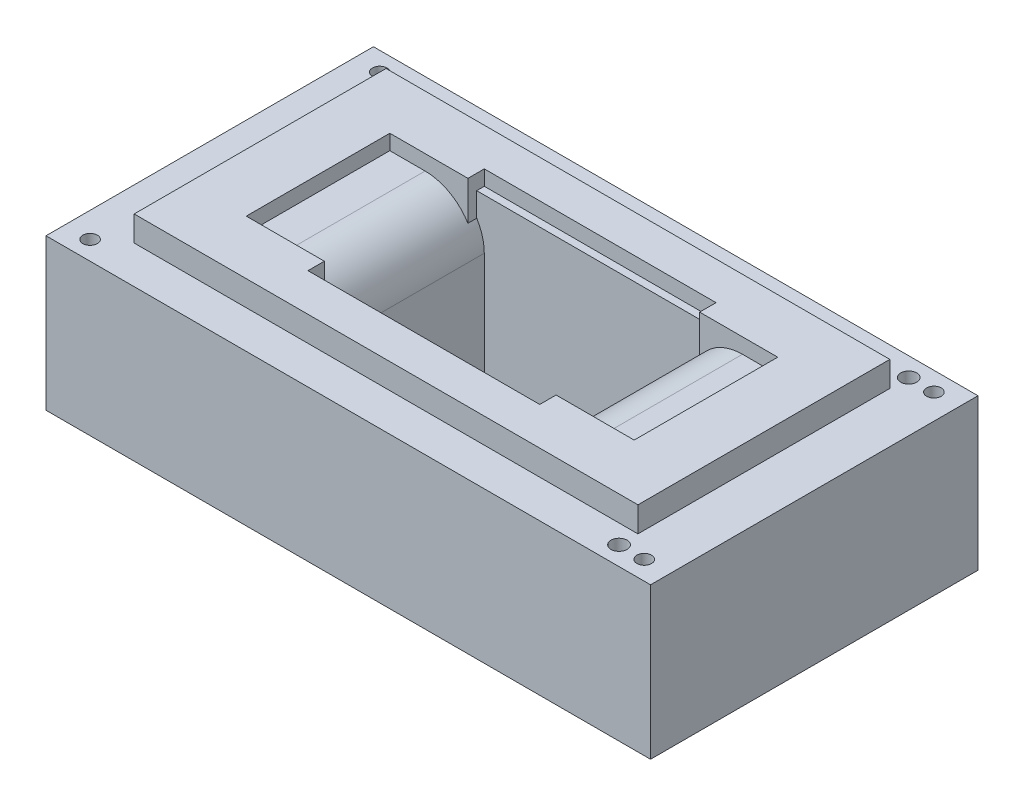
SolidWorks part; units mm, degrees
ref_plane "Front Plane" through (0, 0, 0) normal (0, 0, 1) x (1, 0, 0)
ref_plane "Top Plane" through (0, 0, 0) normal (0, 1, 0) x (1, 0, 0)
ref_plane "Right Plane" through (0, 0, 0) normal (1, 0, 0) x (0, 0, -1)
sketch "Sketch1" plane through (0, 0, 0) normal (0, 1, 0) x (1, 0, 0)
  line L0 (23, -14.25) -> (23, -17.5)
  line L7 (-50, 25) -> (50, 25)
  line L8 (-50, 25) -> (-50, -25)
  line L9 (-50, -25) -> (50, -25)
  line L10 (50, 25) -> (50, -25)
  line L11 (-50, 25) -> (50, -25) construction
  line L12 (-50, -25) -> (23, 11.5) construction
  line L15 (-38.5, 14.25) -> (-23, 14.25)
  line L16 (-38.5, 14.25) -> (-38.5, -14.25)
  line L17 (-38.5, -14.25) -> (-23, -14.25)
  line L18 (38.5, 14.25) -> (38.5, -14.25)
  line L19 (-38.5, 14.25) -> (38.5, -14.25) construction
  line L20 (-38.5, -14.25) -> (38.5, 14.25) construction
  line L21 (-23, 17.5) -> (23, 17.5)
  line L22 (-23, 17.5) -> (-23, 14.25)
  line L23 (-23, -17.5) -> (23, -17.5)
  line L24 (23, 17.5) -> (23, 14.25)
  line L25 (-23, 17.5) -> (23, -17.5) construction
  line L26 (-23, -17.5) -> (23, 17.5) construction
  line L27 (-23, -14.25) -> (-23, -17.5)
  line L28 (28.5, 14.25) -> (50, 25) construction
  line L29 (23, -14.25) -> (38.5, -14.25)
  line L30 (23, 14.25) -> (38.5, 14.25)
  point P0 (0, 0)
  point P1 (0, 0)
  point P2 (0, 0)
  point P6 (0, 0)
  point P17 (0, 0)
  point P18 (0, 0)
  dimension "D1" = 28.5
  dimension "D2" = 77
  dimension "D3" = 50
  dimension "D4" = 100
  dimension "D5" = 46
  dimension "D6" = 35
extrude "Boss-Extrude3" add sketch "Sketch1" along normal blind 2 contours L16 L17 L27 L23 L0 L29 L18 L30 L24 L21 L22 L15
extrude "Boss-Extrude4" add sketch "Sketch1<6>" along normal blind 5
sketch "Sketch1<6>" plane through (0, 0, 0) normal (0, 1, 0) x (1, 0, 0) same geometry as "Sketch1"
sketch "Sketch2" plane through (0, 0, 0) normal (0, -1, 0) x (1, 0, 0)
  line L0 (-60, 32.5) -> (-50, 25) construction
  line L1 (-60, 32.5) -> (60, 32.5)
  line L2 (-60, 32.5) -> (-60, -32.5)
  line L3 (-60, -32.5) -> (60, -32.5)
  line L4 (60, 32.5) -> (60, -32.5)
  line L5 (-60, 32.5) -> (60, -32.5) construction
  line L6 (-60, -32.5) -> (60, 32.5) construction
  line L7 (-55.7374, 27.7668) -> (-54.2626, 29.7332) construction
  line L8 (0, 0) -> (0, -0.0408) construction
  line L9 (-0.0011, 0) -> (0.0027, 0) construction
  circle A0 centre (-55, 28.75) radius 1.45
  circle A1 centre (55, 28.75) radius 1.45
  circle A2 centre (55, -28.75) radius 1.45
  circle A3 centre (-55, -28.75) radius 1.45
  circle A4 centre (50, 28.75) radius 1.6
  circle A5 centre (50, -28.75) radius 1.6
  point P0 (0, 0)
  point P14 (-55, 28.75)
  point P27 (0, 0)
  dimension "D3" = 2.9
  dimension "D4" = 105
  dimension "D5" = 3.2
  dimension "D1" = 65
  dimension "D2" = 120
extrude "Boss-Extrude5" add sketch "Sketch2" along normal blind 30
sketch "Sketch3" plane through (0, -30, 0) normal (0, -1, 0) x (-1, 0, 0)
extrude "Boss-Extrude6" add sketch "Sketch2<2>" along normal blind 3
sketch "Sketch2<2>" plane through (0, 0, 0) normal (0, -1, 0) x (1, 0, 0) same geometry as "Sketch2"
sketch "Sketch6" plane through (0, 5, 0) normal (0, 1, 0) x (1, 0, 0)
  line L0 (-60, 32.5) -> (60, 32.5) construction
  line L5 (-38.5, 14.25) -> (-38.5, 20.6736) construction
  line L6 (60, -32.5) -> (-60, -32.5) construction
  line L7 (0.9, -32.5) -> (20.9, -32.5)
  line L8 (0.9, -32.5) -> (0.9, -7.9646)
  line L9 (0.9, -7.9646) -> (20.9, -7.9646)
  line L10 (20.9, -32.5) -> (20.9, -7.9646)
  line L11 (-38.5, -14.25) -> (-23, -14.25) construction
  line L12 (-38.5, 20.6736) -> (38.5, 20.6736) construction
  line L13 (38.5, 14.25) -> (38.5, 20.6736) construction
  line L14 (0, 20.6736) -> (0, -12.65) construction
  line L19 (-38.5, 14.25) -> (-38.5, -14.25) construction
  line L20 (-38.05, 0) -> (56.245, 0) construction
  line L21 (-0.9, 32.5) -> (-0.9, 8)
  line L22 (-0.9, 32.5) -> (-20.9, 32.5)
  line L23 (-20.9, 32.5) -> (-20.9, 8)
  line L24 (-0.9, 8) -> (-20.9, 8)
  line L25 (60, -32.5) -> (-60, -32.5) construction
  line L26 (-38.5, -14.25) -> (38.5, -14.25) construction
  point P6 (8.6777, -14.25)
  dimension "D1" = 20
  dimension "D2" = 10
  dimension "D3" = 0.9
  dimension "D4" = 0.9
  dimension "D5" = 20
  dimension "D6" = 24.5
sketch "Sketch7" plane through (0, 2, 0) normal (0, 1, 0) x (1, 0, 0)
  line L14 (-21.5, 16) -> (21.5, 16)
  line L15 (-21.5, 16) -> (-21.5, -16)
  line L16 (-21.5, -16) -> (21.5, -16)
  line L17 (21.5, 16) -> (21.5, -16)
  line L18 (-21.5, 16) -> (21.5, -16) construction
  line L19 (-21.5, -16) -> (21.5, 16) construction
  line L20 (23, 17.5) -> (-23, 17.5) construction
  line L21 (-23, -17.5) -> (23, -17.5) construction
  line L22 (23, 14.25) -> (23, 17.5) construction
  line L24 (-23, -14.25) -> (-23, -17.5) construction
  point P4 (0, 0)
  point P5 (0, 0)
  point P13 (0, 0)
  point P15 (0, 0)
  point P17 (0, 0)
  point P18 (-23, -15.875)
  dimension "D1" = 1.5
  dimension "D2" = 1.5
  dimension "D3" = 1.5
  dimension "D4" = 1.5
extrude "Cut-Extrude1" cut sketch "Sketch7" against normal up to next
fillet "Fillet1" radius 10 2 edges at (21.5, 2, 0) (-21.5, 2, 0)
